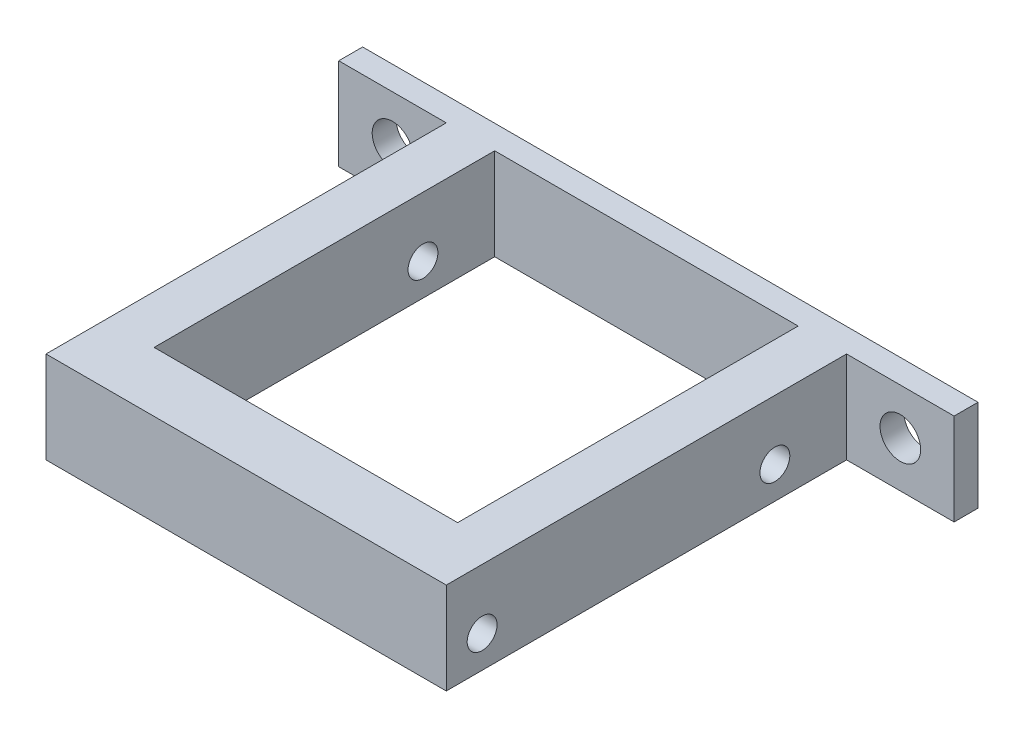
SolidWorks part; units mm, degrees
ref_plane "Front Plane" through (0, 0, 0) normal (0, 0, 1) x (1, 0, 0)
ref_plane "Top Plane" through (0, 0, 0) normal (0, 1, 0) x (1, 0, 0)
ref_plane "Right Plane" through (0, 0, 0) normal (1, 0, 0) x (0, 0, -1)
sketch "Sketch25" plane through (0, 0, 0) normal (0, 1, 0) x (1, 0, 0)
  line L1 (25.75, 28.75) -> (-25.75, 28.75)
  line L2 (25.75, 28.75) -> (25.75, 26.75)
  line L3 (25.75, 26.75) -> (16.75, 26.75)
  line L4 (-25.75, 28.75) -> (-25.75, 26.75)
  line L5 (16.75, -6.75) -> (-16.75, -6.75)
  line L6 (16.75, 26.75) -> (16.75, -6.75)
  line L8 (12.7, 26.75) -> (12.7, -1.75)
  line L9 (-16.75, 26.75) -> (-25.75, 26.75)
  line L10 (12.7, 26.75) -> (-12.7, 26.75)
  line L11 (-16.75, 26.75) -> (-16.75, -6.75)
  line L13 (-12.7, 26.75) -> (-12.7, -1.75)
  line L16 (-12.7, -1.75) -> (12.7, -1.75)
  point P7 (0, -6.75)
  point P14 (0, -1.75)
  dimension "D1" = 9
  dimension "D2" = 9
  dimension "D3" = 25.4
  dimension "D4" = 33.5
  dimension "D5" = 51.5
  dimension "D6" = 2
  dimension "D7" = 5
extrude "Boss-Extrude5" add sketch "Sketch25" against normal blind 7.68 separate body
hole_wizard "M3x0.5 Tapped Hole2" positions "3DSketch4" profile "Sketch6" tap size "M3x0.5" standard "ANSI Metric"
sketch3d "3DSketch4"
  line L3 (16.75, -7.68, 6.75) -> (16.75, 0, 6.75) construction
  line L4 (16.75, -7.68, 6.75) -> (16.75, -7.68, -26.75) construction
  line L5 (16.75, 0, 6.75) -> (16.75, 0, -26.75) construction
  line L9 (16.75, -7.68, -8.5) -> (16.75, 0, -8.5) construction
  line L10 (16.75, -5, -20.75) -> (16.75, -5, 3.75) construction
  point P13 (16.75, -5, 3.75)
  point P15 (16.75, -5, -20.75)
  point P17 (-16.75, -5, -20.75)
  point P26 (-16.75, -5, 3.75)
  point P53 (16.75, -5, -8.5)
  dimension "D1" = 20.25
  dimension "D5" = 3
  dimension "D7" = 2.68
sketch "Sketch6" plane through (16.75, -5, 3.75) normal (0, 1, 0) x (0, 0, -1)
  line L0 (0, 0) -> (0, 8.3711)
  line L1 (0, 8.3711) -> (1.25, 7.62)
  line L2 (1.25, 7.62) -> (1.25, 0)
  line L5 (1.25, 0) -> (0, 0)
  line L10 (0, 8.3711) -> (-1.25, 7.62) construction
  line L11 (0, -6.35) -> (0, 107.95) construction
  dimension "Tap Drill Dia." = 2.5
  dimension "Tap Drill Depth" = 7.62
  dimension "Drill Angle" = 118
hole_wizard "M3 Clearance Hole3" positions "3DSketch7" profile "Sketch23" hole size "M3" standard "ANSI Metric" end condition through all
sketch3d "3DSketch7"
  line L5 (16.75, 0, -26.75) -> (25.75, 0, -26.75) construction
  line L6 (25.75, -7.68, -26.75) -> (25.75, 0, -26.75) construction
  line L8 (-25.75, -7.68, -26.75) -> (-16.75, -7.68, -26.75) construction
  point P0 (21.25, -3.84, -26.75)
  point P2 (-21.25, -3.84, -26.75)
  point P27 (21.25, 0, -26.75)
  point P31 (25.75, -3.84, -26.75)
  point P38 (-21.25, -7.68, -26.75)
sketch "Sketch23" plane through (21.25, -3.84, -26.75) normal (1, 0, 0) x (0, -1, 0)
  line L0 (0, 0) -> (0, 2)
  line L1 (0, 2) -> (1.7, 2)
  line L2 (1.7, 2) -> (1.7, 0)
  line L5 (1.7, 0) -> (0, 0)
  line L11 (0, -6.35) -> (0, 107.95) construction
  dimension "Thru Hole Dia." = 3.4
  dimension "Thru Hole Depth" = 2
